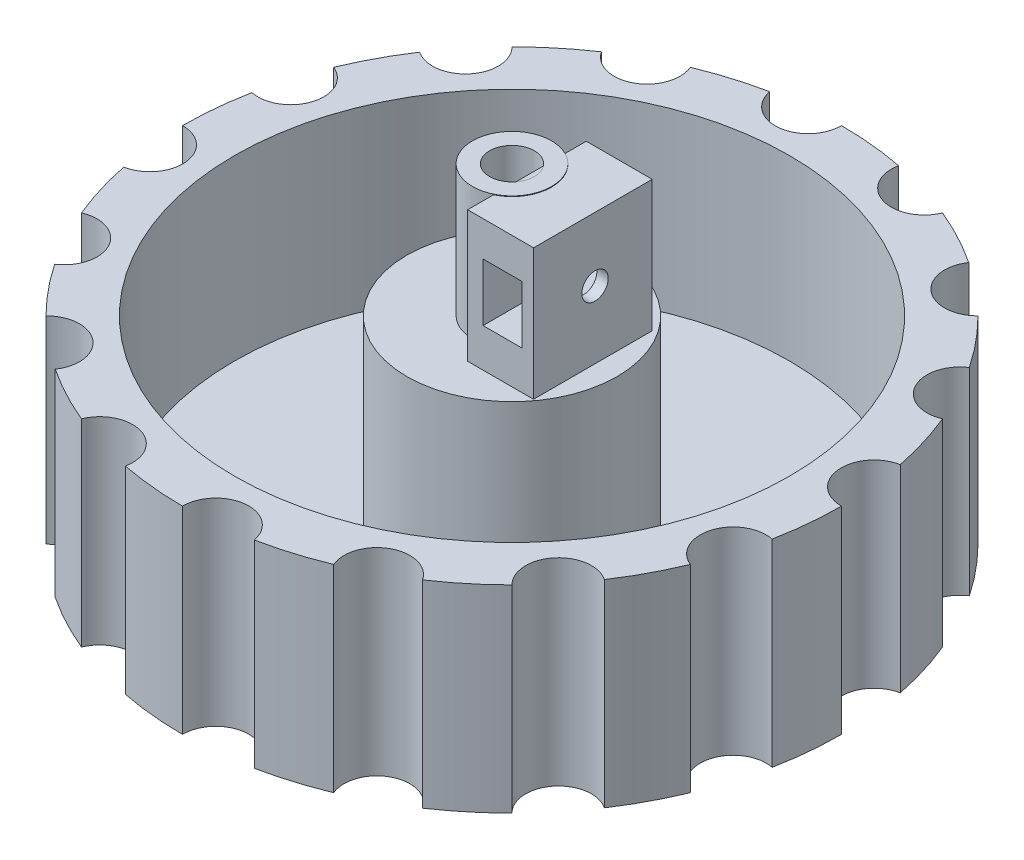
SolidWorks part; units mm, degrees
ref_plane "Front Plane" through (0, 0, 0) normal (0, 0, 1) x (1, 0, 0)
ref_plane "Top Plane" through (0, 0, 0) normal (0, 1, 0) x (1, 0, 0)
ref_plane "Right Plane" through (0, 0, 0) normal (1, 0, 0) x (0, 0, -1)
sketch "Sketch1" plane through (0, 0, 0) normal (0, 1, 0) x (1, 0, 0)
  circle A0 centre (0, 0) radius 6
extrude "Boss-Extrude1" add sketch "Sketch1" along normal blind 20
sketch "Sketch2" plane through (0, 20, 0) normal (0, 1, 0) x (1, 0, 0)
  circle A0 centre (0, 0) radius 3.4
extrude "Cut-Extrude1" cut sketch "Sketch2" against normal blind 13.55 contours A0
ref_plane "Plane1" through (0, 18.26, 0) normal (0, 1, 0) x (1, 0, 0)
ref_axis "Axis1" through (0, 6.45, 0) along (0, 1, 0)
ref_point "Point2"
sketch "Sketch5" plane through (0, 18.26, 0) normal (0, 1, 0) x (1, 0, 0)
  line L0 (0, 0) -> (2.6, 0) construction
  line L2 (2.6, -3.5716) -> (4.1507, -3.5716)
  line L3 (2.6, -3.5716) -> (2.6, 3.6126)
  line L4 (2.6, 3.6126) -> (4.1507, 3.6126)
  line L5 (4.1507, -3.5716) -> (4.1507, 3.6126)
extrude "Boss-Extrude2" add sketch "Sketch5" against normal blind 13.55
sketch "Sketch7" plane through (2.6, 0, 0) normal (-1, 0, 0) x (0, 0, 1)
  line L1 (-8.6717, 19.91) -> (9.3323, 19.91)
  line L2 (-8.6717, 19.91) -> (-8.6717, 0)
  line L3 (-8.6717, 0) -> (9.3323, 0)
  line L4 (9.3323, 19.91) -> (9.3323, 0)
extrude "Boss-Extrude3" add sketch "Sketch7" against normal blind 10
sketch "Sketch6" plane through (2.6, 0, 0) normal (-1, 0, 0) x (0, 0, 1)
  line L1 (-2.1909, 6.45) -> (-2.1909, 19.91) construction
  line L2 (2.1909, 19.91) -> (2.1909, 6.45) construction
  line L3 (-2.1909, 15.4522) -> (2.1909, 15.4522) construction
  circle A0 centre (0, 10.2369) radius 2
extrude "Cut-Extrude2" cut sketch "Sketch6" against normal blind 13.55 and the other way blind 1
ref_axis "Axis2" through (-1.8994, 10.2369, 0) along (-1, 0, 0)
ref_axis "Axis4" through (12.6, 10.2369, 0) along (-1, 0, 0)
ref_plane "Plane3" through (0, 0, 0) normal (0, 0, 1) x (1, 0, 0)
sketch "Sketch9" plane through (0, 0, 0) normal (0, 0, 1) x (1, 0, 0)
  line L0 (10.8765, 10.2369) -> (10.8765, 5.8619)
  line L1 (4.9434, 5.8619) -> (10.8765, 5.8619)
  line L2 (4.9434, 5.8619) -> (4.9434, 10.2369)
  line L3 (4.9434, 10.2369) -> (4.9434, 14.6143)
  line L4 (4.9434, 14.6143) -> (10.8765, 14.6143)
  line L5 (10.8765, 14.6143) -> (10.8765, 10.2369)
  line L6 (12.6, 10.2369) -> (2.6, 10.2369) construction
  point P5 (10.8765, 14.6143)
extrude "Cut-Extrude3" cut sketch "Sketch9" against normal blind 10 and the other way blind 10
sketch "Sketch10" plane through (0, 0, 0) normal (0, -1, 0) x (1, 0, 0)
  circle A0 centre (0, 0) radius 50
extrude "Boss-Extrude4" add sketch "Sketch10" along normal blind 30
sketch "Sketch11" plane through (0, 0, 0) normal (0, 1, 0) x (1, 0, 0)
  line L1 (31.7817, 38.8528) -> (14.4942, 48.0577) construction
  line L2 (14.4942, 48.0577) -> (-5, 49.9462) construction
  line L3 (-5, 49.9462) -> (-23.733, 44.2308) construction
  line L4 (-23.733, 44.2308) -> (-38.8528, 31.7817) construction
  line L5 (-38.8528, 31.7817) -> (-48.0577, 14.4942) construction
  line L6 (-48.0577, 14.4942) -> (-49.9462, -5) construction
  line L7 (-49.9462, -5) -> (-44.2308, -23.733) construction
  line L8 (-44.2308, -23.733) -> (-31.7817, -38.8528) construction
  line L9 (-31.7817, -38.8528) -> (-14.4942, -48.0577) construction
  line L10 (-14.4942, -48.0577) -> (5, -49.9462) construction
  line L11 (5, -49.9462) -> (23.733, -44.2308) construction
  line L12 (23.733, -44.2308) -> (38.8528, -31.7817) construction
  line L13 (38.8528, -31.7817) -> (48.0577, -14.4942) construction
  line L14 (48.0577, -14.4942) -> (49.9462, 5) construction
  line L15 (49.9462, 5) -> (44.2308, 23.733) construction
  line L16 (44.2308, 23.733) -> (31.7817, 38.8528) construction
  circle A0 centre (0, 0) radius 49.2313 construction
  circle A1 centre (5, -49.9462) radius 5
  circle A2 centre (-14.4942, -48.0577) radius 5
  circle A3 centre (-31.7817, -38.8528) radius 5
  circle A4 centre (-44.2308, -23.733) radius 5
  circle A5 centre (-49.9462, -5) radius 5
  circle A6 centre (-48.0577, 14.4942) radius 5
  circle A7 centre (-38.8528, 31.7817) radius 5
  circle A8 centre (-23.733, 44.2308) radius 5
  circle A9 centre (-5, 49.9462) radius 5
  circle A10 centre (14.4942, 48.0577) radius 5
  circle A11 centre (31.7817, 38.8528) radius 5
  circle A12 centre (44.2308, 23.733) radius 5
  circle A13 centre (49.9462, 5) radius 5
  circle A14 centre (48.0577, -14.4942) radius 5
  circle A15 centre (38.8528, -31.7817) radius 5
  circle A16 centre (23.733, -44.2308) radius 5
extrude "Cut-Extrude4" cut sketch "Sketch11" against normal up to surface (30 mm away) up to face at (0, -30, -50)
sketch "Sketch12" plane through (0, 0, 0) normal (0, 1, 0) x (1, 0, 0)
  circle A0 centre (0, 0) radius 42.1244
  circle A1 centre (0, 0) radius 15.9579
extrude "Cut-Extrude5" cut sketch "Sketch12" against normal blind 27
